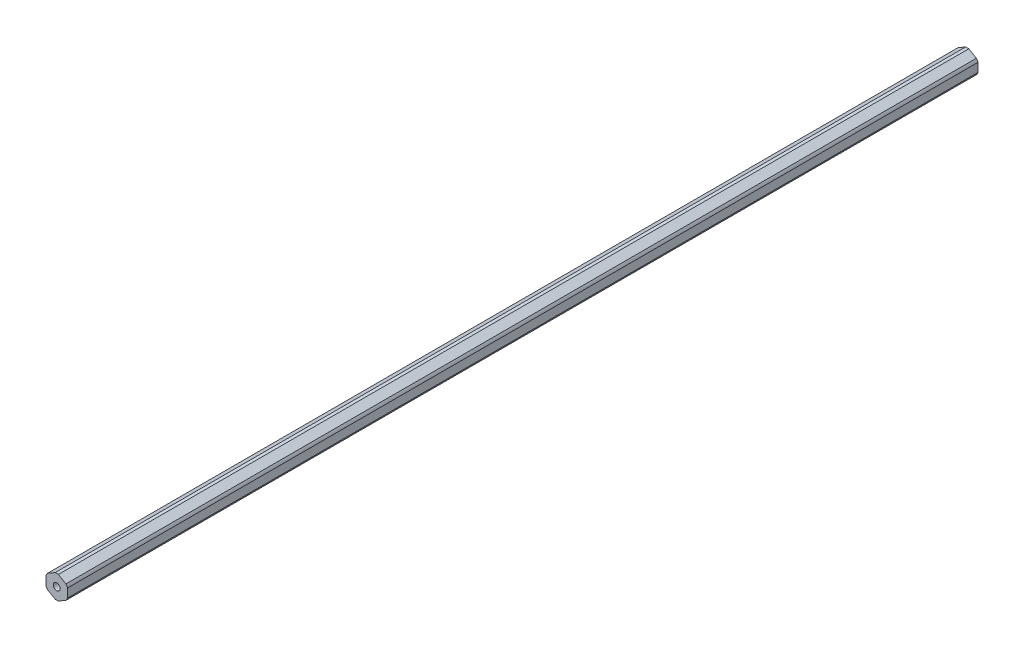
SolidWorks part; units mm, degrees
material "6061-T6 (SS)"
ref_plane "Front Plane" through (0, 0, 0) normal (0, 0, 1) x (1, 0, 0)
ref_plane "Top Plane" through (0, 0, 0) normal (0, 1, 0) x (1, 0, 0)
ref_plane "Right Plane" through (0, 0, 0) normal (1, 0, 0) x (0, 0, -1)
sketch "Sketch1" plane through (0, 0, 0) normal (0, 0, 1) x (1, 0, 0)
  line L1 (0, 7.3323) -> (-6.35, 3.6662)
  line L2 (-6.35, 3.6662) -> (-6.35, -3.6662)
  line L3 (-6.35, -3.6662) -> (0, -7.3323)
  line L4 (0, -7.3323) -> (6.35, -3.6662)
  line L5 (6.35, -3.6662) -> (6.35, 3.6662)
  line L6 (6.35, 3.6662) -> (0, 7.3323)
  circle A0 centre (0, 0) radius 6.35 construction
  circle A1 centre (0, 0) radius 6.858
  dimension "D1" = 12.7
  dimension "D2" = 13.716
extrude "Boss-Extrude1" add sketch "Sketch1" along normal mid plane 536.829 contours L5 A1 L6 L1 L2 L3 L4 region at (0, 0, 0)
sketch "Sketch2" plane through (0, 0, 268.4145) normal (0, 0, 1) x (1, 0, 0)
  circle A0 centre (0, 0) radius 2.0193
  dimension "D1" = 4.0386
extrude "Cut-Extrude1" cut sketch "Sketch2" against normal through all
